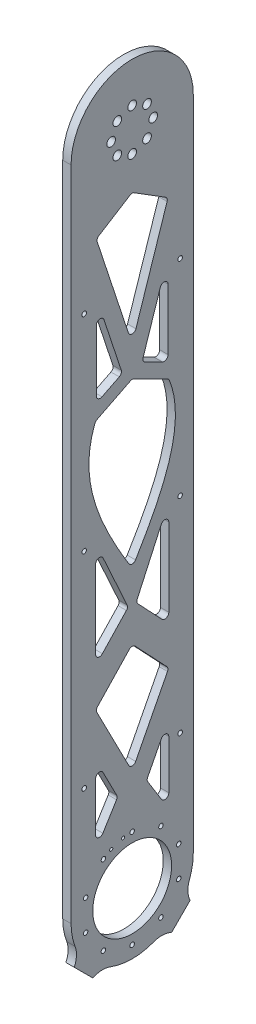
SolidWorks part; units mm, degrees
material "6061 Alloy"
ref_plane "Front Plane" through (0, 0, 0) normal (0, 0, 1) x (1, 0, 0)
ref_plane "Top Plane" through (0, 0, 0) normal (0, 1, 0) x (1, 0, 0)
ref_plane "Right Plane" through (0, 0, 0) normal (1, 0, 0) x (0, 0, -1)
sketch "Sketch1" plane through (0, 0, 0) normal (1, 0, 0) x (0, -1, 0)
  line L0 (0, 0) -> (500, 0) construction
  line L1 (0, 46.5) -> (500, 46.5)
  line L2 (0, -46.5) -> (500, -46.5)
  arc A0 (0, 46.5) -> (0, -46.5) centre (0, 0) ccw
  arc A1 (500, -46.5) -> (500, 46.5) centre (500, 0) ccw
  circle A2 centre (0, 0) radius 16 construction
  circle A3 centre (-16, 0) radius 3.3
  circle A4 centre (-11.3137, 11.3137) radius 3.3
  circle A5 centre (0, 16) radius 3.3
  circle A6 centre (11.3137, 11.3137) radius 3.3
  circle A7 centre (16, 0) radius 3.3
  circle A8 centre (11.3137, -11.3137) radius 3.3
  circle A27 centre (500, 0) radius 37.25 construction
  circle A28 centre (537.25, 0) radius 1.7
  circle A29 centre (500, 0) radius 37.25 construction
  circle A30 centre (537.25, 0) radius 1.7
  circle A31 centre (530.1359, -21.895) radius 1.7
  circle A32 centre (511.5109, -35.4269) radius 1.7
  circle A33 centre (488.4891, -35.4269) radius 1.7
  circle A34 centre (469.8641, -21.895) radius 1.7
  circle A35 centre (462.75, 0) radius 1.7
  circle A36 centre (469.8641, 21.895) radius 1.7
  circle A37 centre (488.4891, 35.4269) radius 1.7
  circle A38 centre (511.5109, 35.4269) radius 1.7
  circle A39 centre (530.1359, 21.895) radius 1.7
  circle A40 centre (500, 0) radius 26
  circle A41 centre (0, -16) radius 3.3
  circle A42 centre (-11.3137, -11.3137) radius 3.3
  point P3 (250, 0)
  point P25 (0, 0)
  point P52 (500, 0)
  point P61 (500, 0)
  dimension "D3" = 32
  dimension "D4" = 6.6
  dimension "D2" = 74.5
  dimension "D7" = 3.4
  dimension "D8" = 3.4
  dimension "D10" = 52
  dimension "D6" = 46.5
  dimension "D1" = 500
  dimension "D5" = 8
  dimension "D9" = 10
extrude "Boss-Extrude1" add sketch "Sketch1" along normal blind 6.35 contours L2 A1 L1 A0 A40 A39 A38 A37 A36 A35 A34 A33 A32 A31 A28 A8 A7 A6 A5 A4 A3 region at (0, -240.4496, 0)
ref_axis "Axis1" through (6.35, -500, 0) along (-1, 0, 0)
sketch "Sketch3" plane through (6.35, 0, 0) normal (1, 0, 0) x (0, 0, -1)
  line L0 (0, -500) -> (0, 0) construction
  line L1 (0, -422.848) -> (27.8582, -368.6328)
  line L2 (0, -422.848) -> (-27.8582, -368.6328)
  line L3 (-27.8582, -368.6328) -> (0, -339.1393)
  line L4 (0, -339.1393) -> (27.8582, -368.6328)
  line L5 (0, -41.3687) -> (-27.3129, -58.4352)
  line L6 (-27.3129, -58.4352) -> (0, -141.249)
  line L7 (0, -141.249) -> (27.3129, -58.4352)
  line L8 (27.3129, -58.4352) -> (0, -41.3687)
  line L9 (3, -313.1891) -> (27.8582, -339.5065)
  line L10 (27.8582, -339.5065) -> (27.8582, -258.646)
  line L11 (27.8582, -258.646) -> (3, -313.1891)
  line L12 (-27.8582, -339.5065) -> (-27.8582, -258.646)
  line L13 (-3, -313.1891) -> (-27.8582, -339.5065)
  line L14 (-27.8582, -258.646) -> (-3, -313.1891)
  line L15 (-27.8582, -401.4529) -> (-11, -434.2608)
  line L16 (-11, -434.2608) -> (-27.8582, -461.4818)
  line L17 (-27.8582, -461.4818) -> (-27.8582, -401.4529)
  line L18 (11, -434.2608) -> (27.8582, -461.4818)
  line L19 (27.8582, -401.4529) -> (11, -434.2608)
  line L20 (27.8582, -461.4818) -> (27.8582, -401.4529)
  line L21 (0, -164.2489) -> (-27.8582, -178.2005)
  line L22 (0, -164.2489) -> (27.8582, -178.2005)
  line L23 (7.5, -156.821) -> (27.3129, -96.7475)
  line L24 (27.3129, -96.7475) -> (27.3129, -166.7434)
  line L25 (27.3129, -166.7434) -> (7.5, -156.821)
  line L26 (-27.3129, -96.7475) -> (-27.3129, -166.7434)
  line L27 (-7.5, -156.821) -> (-27.3129, -96.7475)
  line L28 (-27.3129, -166.7434) -> (-7.5, -156.821)
  spline S0 degree 3 poles (-27.8582, -178.2005) (-43.7791, -216.0933) (-18.6166, -258.2761) (0, -289.085) knots 0 0 0 0 1 1 1 1
  spline S1 degree 3 poles (27.8582, -178.2005) (43.7791, -216.0933) (18.6166, -258.2761) (0, -289.085) knots 0 0 0 0 1 1 1 1
  dimension "D1" = 15
  dimension "D2" = 20
  dimension "D3" = 12
  dimension "D4" = 10
  dimension "D5" = 6
  dimension "D6" = 15
  dimension "D7" = 22
extrude "Cut-Extrude1" cut sketch "Sketch3" against normal through all
fillet "Fillet1" radius 3 30 edges at (3.175, -58.4352, -27.3129) (3.175, -41.3687, 0) (3.175, -58.4352, 27.3129) (3.175, -141.249, 0) (3.175, -289.085, 0) (3.175, -164.2489, 0) (3.175, -401.4529, 27.8582) (3.175, -434.2608, 11) (3.175, -461.4818, 27.8582) (3.175, -461.4818, -27.8582) (3.175, -434.2608, -11) (3.175, -401.4529, -27.8582) (3.175, -368.6328, -27.8582) (3.175, -339.1393, 0) (3.175, -368.6328, 27.8582) (3.175, -422.848, 0) (3.175, -313.1891, 3) (3.175, -339.5065, 27.8582) (3.175, -258.646, 27.8582) (3.175, -178.2005, -27.8582) (3.175, -178.2005, 27.8582) (3.175, -339.5065, -27.8582) (3.175, -313.1891, -3) (3.175, -258.646, -27.8582) (3.175, -96.7475, 27.3129) (3.175, -166.7434, 27.3129) (3.175, -156.821, 7.5) (3.175, -166.7434, -27.3129) (3.175, -156.821, -7.5) (3.175, -96.7475, -27.3129)
sketch "Sketch4" plane through (6.35, 0, 0) normal (1, 0, 0) x (0, 0, -1)
  line L0 (0, 46.5) -> (-113.1579, 46.5) construction
  line L1 (-46.5, 0) -> (-46.5, -500) construction
  line L2 (-46.5, -100) -> (46.5, -100) construction
  line L3 (46.5, 0) -> (46.5, -500) construction
  line L4 (-46.5, -106.35) -> (46.5, -106.35) construction
  line L5 (-36.5, -100) -> (-36.5, -106.35) construction
  line L6 (0, 0) -> (0, -106.35) construction
  line L7 (0, -106.35) -> (0, -256.35) construction
  line L8 (0, -256.35) -> (46.5, -256.35) construction
  line L9 (46.5, -262.7) -> (-46.5, -262.7) construction
  line L10 (0, -181.35) -> (46.5, -181.35) construction
  line L11 (0, -262.7) -> (0, -412.7) construction
  line L12 (0, -412.7) -> (46.5, -412.7) construction
  line L13 (0, -337.7) -> (46.5, -337.7) construction
  arc A1 (46.5, 0) -> (-46.5, 0) centre (0, 0) ccw construction
  circle A2 centre (-36.5, -103.175) radius 1.75
  circle A3 centre (36.5, -103.175) radius 1.75
  circle A4 centre (-36.5, -259.525) radius 1.75
  circle A5 centre (36.5, -259.525) radius 1.75
  circle A6 centre (-36.5, -415.875) radius 1.75
  circle A7 centre (36.5, -415.875) radius 1.75
  point P17 (-36.5, -103.175)
  dimension "D1" = 3.5
  dimension "D2" = 6.35
  dimension "D3" = 10
  dimension "D4" = 146.5
  dimension "D5" = 150
  dimension "D6" = 6.35
  dimension "D7" = 81.35
  dimension "D8" = 150
  dimension "D9" = 81.35
extrude "Cut-Extrude2" cut sketch "Sketch4" against normal through all
sketch "Sketch5" plane through (6.35, 0, 0) normal (1, 0, 0) x (0, 0, -1)
  line L0 (-6.9161, -463.3431) -> (-15.9511, -466.2787) construction
  line L1 (-7.2252, -475.0096) -> (7.4545, -470.2399) construction
  line L2 (-21.895, -469.8641) -> (0, -462.75) construction
  line L3 (-10.9475, -466.3071) -> (0, -500) construction
  circle A0 centre (-6.9161, -463.3431) radius 1.2
  circle A1 centre (-15.9511, -466.2787) radius 1.2
  circle A2 centre (0, -500) radius 26 construction
  circle A3 centre (0, -500) radius 26 construction
  circle A4 centre (0, -462.75) radius 1.7 construction
  circle A5 centre (-21.895, -469.8641) radius 1.7 construction
  circle A6 centre (0, -462.75) radius 1.7 construction
  circle A7 centre (-21.895, -469.8641) radius 1.7 construction
  point P16 (-11.4336, -464.8109)
  dimension "D1" = 2.4
  dimension "D2" = 9.5
  dimension "D3" = 11
extrude "Cut-Extrude4" cut sketch "Sketch5" against normal through all
sketch "Sketch6" plane through (6.35, 0, 0) normal (1, 0, 0) x (0, 0, -1)
  line L2 (-23.6842, -540.0163) -> (-29.9682, -544.1104) construction
  line L3 (-44.1104, -529.9682) -> (-29.9682, -544.1104)
  line L4 (0, -500) -> (0, -546.5) construction
  line L5 (-37.0393, -537.0393) -> (0, -500) construction
  line L6 (-44.1104, -529.9682) -> (-40.0163, -523.6842) construction
  arc A0 (-46.5, -500) -> (46.5, -500) centre (0, -500) ccw construction
  arc A1 (-29.9682, -544.1104) -> (-16.4747, -543.4837) centre (-22.4977, -559.381) cw
  arc A4 (-44.1104, -529.9682) -> (-43.4837, -516.4747) centre (-59.381, -522.4977) ccw
  arc A5 (-16.4747, -543.4837) -> (-43.4837, -516.4747) centre (0, -500) cw
  dimension "D2" = 17
  dimension "D4" = 17
  dimension "D1" = 20
  dimension "D3" = 8
  dimension "D5" = 8
  dimension "D6" = 7.5
  dimension "D7" = 45
  dimension "D8" = 7.5
extrude "Boss-Extrude2" add sketch "Sketch6" against normal up to surface (6.35 mm away) up to face at (0, -463.3431, 5.7161)
sketch "Sketch7" plane through (0, -287.0393, 287.0393) normal (0, -0.7071, 0.7071) x (1, 0, 0)
  line L0 (0, -343.5534) -> (6.35, -343.5534) construction
  line L1 (0, -363.5534) -> (6.35, -363.5534) construction
  line L2 (0, -363.5534) -> (0, -343.5534) construction
  point P0 (3.175, -347.5534)
  point P1 (3.175, -360.5841)
  dimension "D1" = 4
  dimension "D2" = 2.9693
  dimension "D3" = 3.175
hole_wizard "Tap Drill for M3x0.5 Tap1" positions "Sketch7" profile "Sketch8" hole size "M3x0.5" standard "ANSI Metric"
sketch "Sketch8" plane through (3.175, -532.7967, 41.282) normal (1, 0, 0) x (0, -0.7071, -0.7071)
  line L0 (0, 0) -> (0, 5.7511)
  line L1 (0, 5.7511) -> (1.25, 5)
  line L2 (1.25, 5) -> (1.25, 0)
  line L5 (1.25, 0) -> (0, 0)
  line L10 (0, 5.7511) -> (-1.25, 5) construction
  line L11 (0, -6.35) -> (0, 107.95) construction
  dimension "Hole Dia." = 2.5
  dimension "Hole Depth" = 5
  dimension "Drill Angle" = 118
pattern_circular "CirPattern1" count 2 every 90 about axis through (6.35, -500, 0) along (-1, 0, 0) of "Boss-Extrude2", "Tap Drill for M3x0.5 Tap1" reverse direction yes
sketch "Sketch10" plane through (6.35, 0, 0) normal (1, 0, 0) x (0, 0, -1)
  circle A0 centre (0, -500) radius 30
  circle A1 centre (0, -500) radius 26 construction
  dimension "D1" = 60
extrude "Cut-Extrude6" cut sketch "Sketch10" against normal through all
equation "\"L1L\"=500"
equation "\"D1@Sketch1\"=\"L1L\""
equation "\"L1Thick\"=6.35"
equation "\"D1@Boss-Extrude1\"=\"L1Thick\""
equation "\"Harm-Drive-Outer\"=74.5"
equation "\"D2@Sketch1\"=\"Harm-Drive-Outer\""
